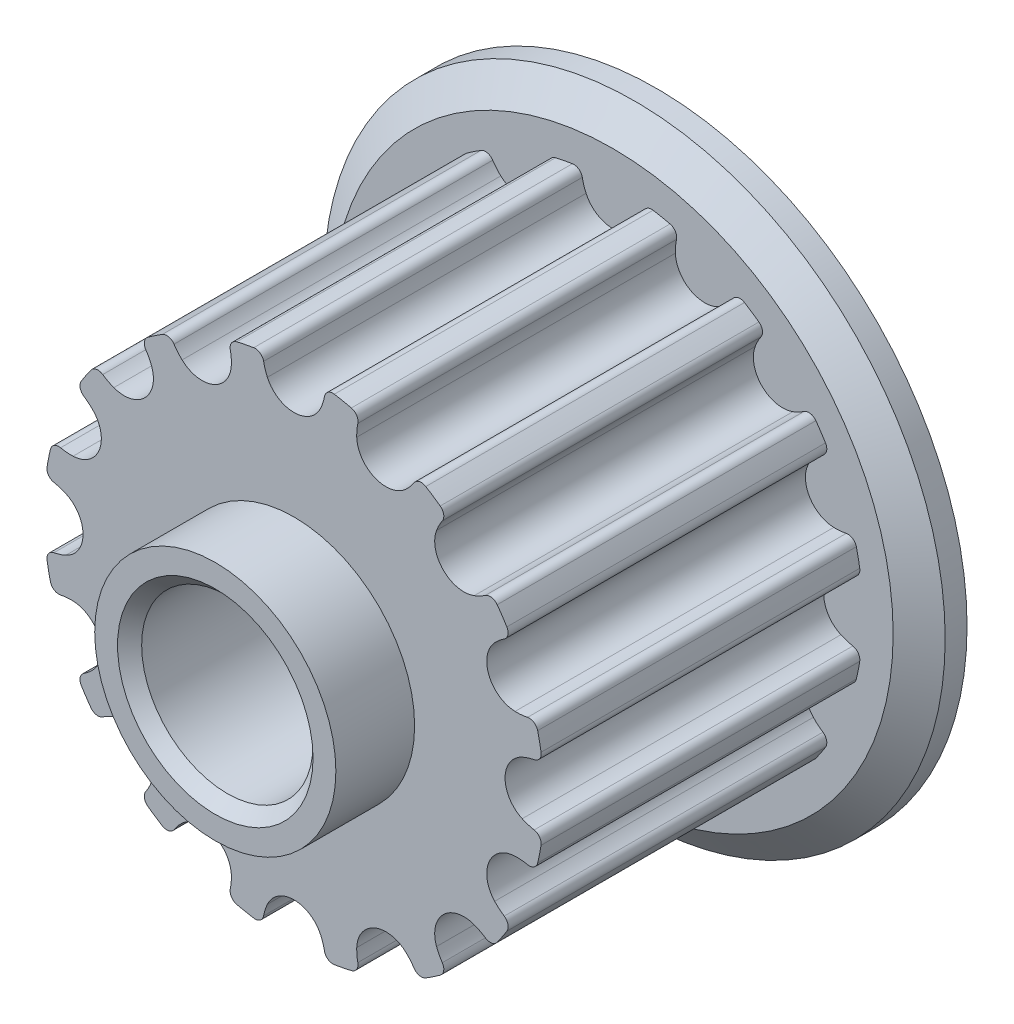
SolidWorks part; units mm, degrees
ref_plane "Front Plane" through (0, 0, 0) normal (0, 0, 1) x (1, 0, 0)
ref_plane "Top Plane" through (0, 0, 0) normal (0, 1, 0) x (1, 0, 0)
ref_plane "Right Plane" through (0, 0, 0) normal (1, 0, 0) x (0, 0, -1)
sketch "Sketch1" plane through (0, 0, 0) normal (0, 0, 1) x (1, 0, 0)
  line L1 (-2.553, 6.1245) -> (2.553, 6.1245) construction
  line L4 (0, 0) -> (0, 6.1245) construction
  line L5 (0, 6.1245) -> (0, 12.0664) construction
  line L6 (0, 7.6455) -> (2.9417, 7.0569) construction
  line L7 (2.9417, 7.0569) -> (3.8741, 6.6682) construction
  line L8 (2.9417, 7.0569) -> (2.553, 6.1245) construction
  line L9 (-2.9417, 7.0569) -> (-2.553, 6.1245) construction
  line L10 (-2.7951, 6.7052) -> (-3.7579, 9.015)
  line L11 (-3.7579, 9.015) -> (3.7579, 9.015)
  line L12 (3.7579, 9.015) -> (2.7951, 6.7052)
  circle A0 centre (0, 0) radius 7.6455 construction
  circle A1 centre (0, 0) radius 9.015 construction
  circle A2 centre (0, 0) radius 7.2645 construction
  arc A3 (-0.7739, 6.6229) -> (0.7739, 6.6229) centre (0, 6.9745) ccw
  arc A4 (-0.7739, 6.6229) -> (-0.8836, 6.9694) centre (0.61, 7.2516) cw
  arc A5 (-2.7951, 6.7052) -> (-1.1695, 7.1697) centre (0, 0) cw
  arc A6 (-0.8836, 6.9694) -> (-1.1695, 7.1697) centre (-1.1292, 6.923) ccw
  arc A7 (2.7951, 6.7052) -> (1.1695, 7.1697) centre (0, 0) ccw
  arc A8 (0.8836, 6.9694) -> (1.1695, 7.1697) centre (1.1292, 6.923) cw
  arc A9 (0.7739, 6.6229) -> (0.8836, 6.9694) centre (-0.61, 7.2516) ccw
  point P6 (0, 20.9083)
  point P11 (0, 7.6455)
  point P13 (0, 9.015)
  point P14 (0, 7.2645)
  dimension "D1" = 8.8419
  dimension "D2" = 4.4209
sketch "Sketch2" plane through (0, 0, 0) normal (1, 0, 0) x (0, 0, -1)
  line L0 (-8.775, 2.3812) -> (8.775, 2.3812)
  line L1 (-8.775, 2.3812) -> (-8.775, 9.015)
  line L2 (-3.29, 9.015) -> (-8.775, 9.015)
  line L3 (-3.925, 2.3813) -> (-3.925, 9.015) construction
  line L4 (-3.925, 9.015) -> (-2.655, 9.015) construction
  line L5 (-2.655, 9.015) -> (-2.655, 7.2645) construction
  line L6 (-2.655, 7.2645) -> (7.505, 7.2645)
  line L7 (7.505, 7.2645) -> (7.505, 9.015) construction
  line L8 (7.505, 9.015) -> (8.775, 9.015) construction
  line L9 (8.775, 9.015) -> (8.775, 2.3812)
  line L10 (-8.775, 0) -> (8.775, 0) construction
  line L11 (8.14, 9.015) -> (7.505, 8.1398)
  line L12 (-2.655, 8.1398) -> (-3.29, 9.015)
  line L14 (-2.655, 8.1398) -> (-2.655, 7.2645)
  line L15 (7.505, 7.2645) -> (7.505, 8.1398)
  line L16 (8.14, 9.015) -> (8.775, 9.015)
  arc A0 (-2.655, 8.1398) -> (-3.29, 9.015) centre (-3.5757, 8.1398) ccw construction
  arc A1 (7.505, 8.1398) -> (8.14, 9.015) centre (8.4257, 8.1398) cw construction
  point P12 (-2.655, 8.1398)
  point P14 (-3.29, 9.015)
  point P20 (7.505, 8.1398)
  point P21 (8.14, 9.015)
  point P25 (7.505, 0)
  point P26 (-2.655, 0)
  dimension "OA" = 17.55
  dimension "Bore" = 4.7625
  dimension "Outside Width" = 11.43
  dimension "Inside Width" = 10.16
revolve "Revolve1" add sketch "Sketch2" angle 360 mid plane about L10
sketch "Sketch3" plane through (0, 0, 0) normal (0, 0, 1) x (1, 0, 0)
  line L6 (3.7579, 9.015) -> (-3.7579, 9.015)
  line L7 (2.7951, 6.7052) -> (3.7579, 9.015)
  line L8 (-3.7579, 9.015) -> (-2.7951, 6.7052)
  line L9 (3.7579, 9.015) -> (-3.7579, 9.015)
  line L10 (2.7951, 6.7052) -> (3.7579, 9.015)
  line L11 (-3.7579, 9.015) -> (-2.7951, 6.7052)
  arc A8 (2.7951, 6.7052) -> (1.1695, 7.1697) centre (0, 0) ccw
  arc A9 (1.1695, 7.1697) -> (0.8836, 6.9694) centre (1.1292, 6.923) ccw
  arc A10 (0.7739, 6.6229) -> (0.8836, 6.9694) centre (-0.61, 7.2516) ccw
  arc A11 (-0.7739, 6.6229) -> (0.7739, 6.6229) centre (0, 6.9745) ccw
  arc A12 (-0.8836, 6.9694) -> (-0.7739, 6.6229) centre (0.61, 7.2516) ccw
  arc A13 (-0.8836, 6.9694) -> (-1.1695, 7.1697) centre (-1.1292, 6.923) ccw
  arc A14 (-1.1695, 7.1697) -> (-2.7951, 6.7052) centre (0, 0) ccw
  arc A15 (2.7951, 6.7052) -> (1.1695, 7.1697) centre (0, 0) ccw
  arc A16 (1.1695, 7.1697) -> (0.8836, 6.9694) centre (1.1292, 6.923) ccw
  arc A17 (0.7739, 6.6229) -> (0.8836, 6.9694) centre (-0.61, 7.2516) ccw
  arc A18 (-0.7739, 6.6229) -> (0.7739, 6.6229) centre (0, 6.9745) ccw
  arc A19 (-0.8836, 6.9694) -> (-0.7739, 6.6229) centre (0.61, 7.2516) ccw
  arc A20 (-0.8836, 6.9694) -> (-1.1695, 7.1697) centre (-1.1292, 6.923) ccw
  arc A21 (-1.1695, 7.1697) -> (-2.7951, 6.7052) centre (0, 0) ccw
  dimension "D1" = 0
extrude "Cut-Extrude1" cut sketch "Sketch3" against normal up to vertex (7.505 mm away) from vertex up to point (0, 7.2645, -7.505) starting at point (0, 7.2645, 2.655)
pattern_circular "CirPattern1" count 16 over 360 about axis through (0, 0, 8.775) along (0, 0, 1) of "Cut-Extrude1"
sketch "Sketch4" plane through (0, 0, 0) normal (1, 0, 0) x (0, -1, 0)
  line L0 (0, -2.655) -> (0, -8.775) construction
  line L1 (-2.3812, -8.775) -> (2.3812, -8.775) construction
  line L2 (8.1398, -2.655) -> (-8.1398, -2.655) construction
  circle A0 centre (0, -5.715) radius 1.7526
extrude "Cut-Extrude2" cut sketch "Sketch4" along normal through all
ref_plane "Plane1" through (0, 0, 5.715) normal (0, 0, 1) x (1, 0, 0)
sketch "Sketch5" plane through (0, 0, 5.715) normal (0, 0, 1) x (1, 0, 0)
  line L0 (0, 0) -> (0, 9.015) construction
  line L1 (2.3812, -1.3716) -> (2.3812, 0)
  line L2 (2.7622, -1.7526) -> (8.462, -1.7526)
  line L3 (2.3812, 0) -> (9.015, 0) construction
  line L4 (2.3812, 0) -> (8.843, 0)
  line L5 (8.843, 0) -> (8.843, -1.3716)
  line L6 (2.7622, -1.7526) -> (2.3812, -1.3716)
  line L7 (8.843, -1.3716) -> (8.462, -1.7526)
  circle A0 centre (0, 0) radius 9.015 construction
  circle A1 centre (0, 0) radius 2.3812 construction
  point P2 (2.3812, -1.7526)
  point P11 (8.843, -1.7526)
revolve "Revolve2" add sketch "Sketch5" angle 360 mid plane about L4
sketch "Sketch6" plane through (8.843, 5.3841, 0) normal (-1, 0, 0) x (0, -1, 0)
  line L1 (5.3841, 6.7269) -> (4.5078, 6.2209)
  line L2 (4.5078, 6.2209) -> (4.5078, 5.2091)
  line L3 (4.5078, 5.2091) -> (5.3841, 4.7031)
  line L4 (5.3841, 4.7031) -> (6.2604, 5.2091)
  line L5 (6.2604, 5.2091) -> (6.2604, 6.2209)
  line L6 (6.2604, 6.2209) -> (5.3841, 6.7269)
  circle A0 centre (5.3841, 5.715) radius 0.8763 construction
  dimension "D1" = 1.7526
extrude "Cut-Extrude3" cut sketch "Sketch6" along normal blind 1.3144
pattern_circular "CirPattern3" count 2 over 90 about axis through (0, 0, 8.775) along (0, 0, 1) of "Cut-Extrude2", "Revolve2", "Cut-Extrude3"
chamfer "Chamfer1" distance 0.2807 angle 45 2 edges at (2.3812, 0, 8.775) (9.015, 0, 8.775)
ref_axis "Center Axis 1" through (0, 0, -8.775) along (0, 0, 1)
ref_plane "Contact Plane 1" through (0, 0, 8.775) normal (0, 0, 1) x (1, 0, 0)
ref_plane "Contact Plane 2" through (0, 0, -8.775) normal (0, 0, -1) x (-1, 0, 0)
sketch "Sketch7" plane through (0, 0, 8.775) normal (0, 0, 1) x (1, 0, 0)
  circle A0 centre (0, 0) radius 9.015 construction
  circle A1 centre (0, 0) radius 9.015
extrude "Cut-Extrude4" cut sketch "Sketch7" against normal offset from surface (7.03 mm away) 9.25 up to face at (0, 0, -7.505)
sketch "Sketch8" plane through (0, 0, -8.775) normal (0, 0, -1) x (-1, 0, 0)
  circle A0 centre (0, 0) radius 2.4875
  dimension "D1" = 4.975
extrude "Cut-Extrude5" cut sketch "Sketch8" against normal through all
sketch "Sketch9" plane through (0, 0, 1.745) normal (0, 0, 1) x (1, 0, 0)
  circle A0 centre (0, 0) radius 2.4875 construction
  circle A1 centre (0, 0) radius 2.4875
  circle A2 centre (0, 0) radius 3.5
  dimension "D1" = 7
extrude "Boss-Extrude1" add sketch "Sketch9" along normal blind 2.286
chamfer "Chamfer2" distance 0.35 angle 45 1 edges at (2.4875, 0, 4.031)
equation "\"D2@Sketch1\"= \"D1@Sketch1\" / 2"
equation "\"D1@Sketch6\" = \"Set Screw@Sketch4\" / 2"
equation "\"D1@Cut-Extrude3\" = \"D1@Sketch6\"*.75"
